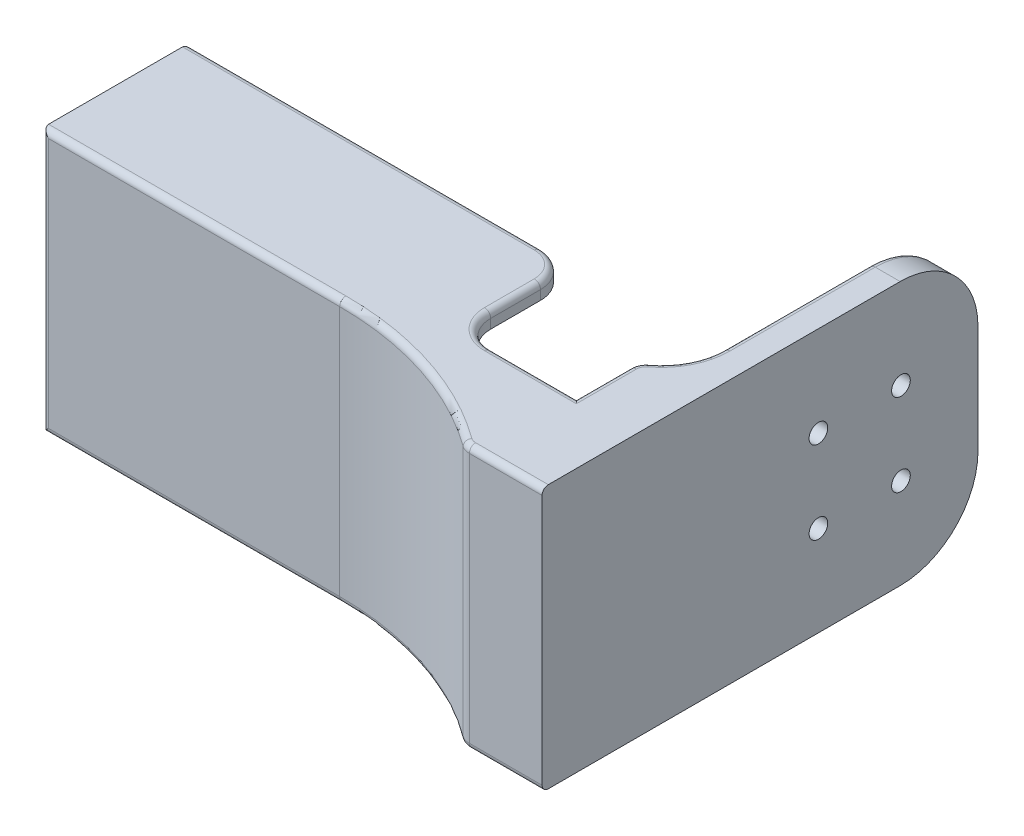
SolidWorks part; units mm, degrees
ref_plane "Alzado" through (0, 0, 0) normal (0, 0, 1) x (1, 0, 0)
ref_plane "Planta" through (0, 0, 0) normal (0, 1, 0) x (1, 0, 0)
ref_plane "Vista lateral" through (0, 0, 0) normal (1, 0, 0) x (0, 0, -1)
sketch "Croquis1" plane through (0, 0, 0) normal (0, 0, 1) x (1, 0, 0)
  line L1 (-59, -42.3) -> (59, -42.3)
  line L2 (-59, -42.3) -> (-59, 42.3)
  line L3 (-59, 42.3) -> (59, 42.3)
  line L4 (59, -42.3) -> (59, 42.3)
  line L5 (-59, -42.3) -> (59, 42.3) construction
  line L6 (-59, 42.3) -> (59, -42.3) construction
  point P0 (0, 0)
  dimension "D1" = 84.6
extrude "Saliente-Extruir1" add sketch "Croquis1" along normal blind 36
sketch "Croquis2" plane through (59, 0, 0) normal (1, 0, 0) x (0, 0, -1)
  line L1 (-36, 42.3) -> (0, 42.3) construction
  line L5 (0, -37.3) -> (0, 37.3)
  line L6 (0, -42.3) -> (0, 42.3) construction
  line L7 (0, 37.3) -> (-36, 37.3)
  line L8 (-36, -42.3) -> (-36, 42.3) construction
  line L9 (-36, 37.3) -> (-36, -37.3)
  line L10 (-36, -37.3) -> (0, -37.3)
  point P5 (0, 0)
  dimension "D1" = 5
extrude "Cortar-Extruir1" cut sketch "Croquis2" against normal blind 120
sketch "Croquis6" plane through (0, -42.3, 0) normal (0, -1, 0) x (1, 0, 0)
  line L0 (-59, 36) -> (59, 36) construction
  line L1 (-59, 0) -> (-59, 36)
  line L2 (-59, 36) -> (0, 36)
  arc A0 (-59, 0) -> (0, 36) centre (8.6236, -44.4803) cw
  point P9 (8.6236, -44.4803)
extrude "Cortar-Extruir3" cut sketch "Croquis6" against normal through all
sketch "Croquis7" plane through (0, 42.3, 0) normal (0, -1, 0) x (1, 0, 0)
  line L1 (59, 36) -> (59, 34)
  line L2 (59, 36) -> (59, 0) construction
  line L8 (-59, 0) -> (-59, 36)
  line L9 (-59, 36) -> (0, 36)
  arc A0 (-59, 0) -> (0, 36) centre (8.6236, -44.4803) cw
extrude "Saliente-Extruir2" add sketch "Croquis7" along normal through all separate body contours L9 A0 L8
sketch "Croquis8" plane through (0, 0, 36) normal (0, 0, 1) x (1, 0, 0)
  line L0 (-59, 42.3) -> (-59, -42.3)
  line L1 (-59, -42.3) -> (101.5, -42.3)
  line L2 (101.5, -42.3) -> (101.5, 42.3)
  line L3 (101.5, 42.3) -> (-59, 42.3)
  dimension "D1" = 160.5
extrude "Saliente-Extruir3" add sketch "Croquis8" along normal blind 5
sketch "Croquis9" plane through (-59, 0, 0) normal (-1, 0, 0) x (0, 0, 1)
  line L0 (0, 42.3) -> (41, 42.3)
  line L1 (41, 42.3) -> (41, -42.3)
  line L2 (41, -42.3) -> (0, -42.3)
  line L3 (0, -42.3) -> (0, 42.3)
extrude "Saliente-Extruir4" add sketch "Croquis9" along normal blind 5
sketch "Croquis10" plane through (0, 0, 36) normal (0, 0, -1) x (-1, 0, 0)
  line L0 (-101.5, 42.3) -> (-96.5, 42.3)
  line L1 (-101.5, 42.3) -> (-59, 42.3) construction
  line L2 (-96.5, 42.3) -> (-96.5, -42.3)
  line L3 (-59, -42.3) -> (-101.5, -42.3) construction
  line L4 (-96.5, -42.3) -> (-101.5, -42.3)
  line L5 (-101.5, -42.3) -> (-101.5, 42.3)
extrude "Saliente-Extruir5" add sketch "Croquis10" along normal blind 20
fillet "Redondeo2" radius 10 4 edges at (59, -39.8, 36) (59, -39.8, 0) (59, 39.8, 36) (59, 39.8, 0)
fillet "Redondeo4" radius 2 11 edges at (82.75, -42.3, 36) (61.9289, -42.3, 33.0711) (59, -42.3, 18) (56.0711, -42.3, 2.9289) (82.75, 42.3, 36) (61.9289, 42.3, 33.0711) (59, 42.3, 18) (56.0711, 42.3, 2.9289) (-7.5, -42.3, 0) (-64, 0, 0) (-7.5, 42.3, 0)
sketch "Croquis18" plane through (0, 0, 41) normal (0, 0, 1) x (1, 0, 0)
  line L0 (-64, 42.3) -> (-64, -42.3)
  line L1 (-64, -42.3) -> (101.5, -42.3)
  line L2 (101.5, -42.3) -> (101.5, 42.3)
  line L3 (101.5, -42.3) -> (101.5, 42.3) construction
  line L4 (101.5, 42.3) -> (-64, 42.3)
extrude "Saliente-Extruir9" add sketch "Croquis18" along normal blind 6
sketch "Croquis23" plane through (101.5, 0, 0) normal (1, 0, 0) x (0, 0, -1)
  line L0 (-47, 42.3) -> (-16, 42.3)
  line L1 (-16, 42.3) -> (-16, -42.3)
  line L2 (-16, -42.3) -> (-47, -42.3)
  line L3 (-47, -42.3) -> (-47, 42.3)
extrude "Saliente-Extruir12" add sketch "Croquis23" along normal blind 5
sketch "Croquis19" plane through (106.5, 0, 0) normal (1, 0, 0) x (0, 0, -1)
  line L0 (-47, 42.3) -> (73, 42.3)
  line L2 (-47, 42.3) -> (-47, -42.3)
  line L3 (-47, -42.3) -> (73, -42.3)
  line L4 (73, -42.3) -> (73, 42.3)
extrude "Saliente-Extruir10" add sketch "Croquis19" along normal blind 10
sketch "Croquis31" plane through (0, 42.3, 0) normal (0, 1, 0) x (1, 0, 0)
  line L0 (106.5, -16) -> (96.5, -16) construction
  line L1 (96.5, -16) -> (106.5, -16) construction
fillet "Redondeo6" radius 20 1 edges at (106.5, 0, 16)
fillet "Redondeo9" radius 5 1 edges at (96.5, 0, 16)
sketch "Croquis22" plane through (0, 0, 47) normal (0, 0, 1) x (1, 0, 0)
  line L0 (116.5, 42.3) -> (91.5, 42.3)
  line L1 (116.5, 42.3) -> (-64, 42.3) construction
  line L2 (91.5, 42.3) -> (91.5, -42.3)
  line L3 (-64, -42.3) -> (116.5, -42.3) construction
  line L4 (91.5, -42.3) -> (116.5, -42.3)
  line L5 (116.5, -42.3) -> (116.5, 42.3)
extrude "Saliente-Extruir11" add sketch "Croquis22" along normal blind 20
fillet "Redondeo7" radius 100 1 edges at (91.5, 0, 47)
fillet "Redondeo10" radius 5 1 edges at (91.5, 0, 67)
sketch "Croquis24" plane through (0, 42.3, 0) normal (0, 1, 0) x (1, 0, 0)
  line L0 (-64, -2) -> (-64, 10) construction
  line L1 (-64, -47) -> (-64, -2) construction
  line L2 (-64, 10) -> (99.396, 10) construction
  line L3 (-64, 10) -> (-64, 35) construction
  line L4 (-64, 35) -> (125.652, 35) construction
  arc A0 (-62, 0) -> (-64, -2) centre (-62, -2) ccw construction
sketch "Croquis25" plane through (106.5, 0, 0) normal (-1, 0, 0) x (0, 0, 1)
  line L0 (-35, 42.3) -> (-35, -42.3) construction
  line L1 (-10, 42.3) -> (-35, 42.3) construction
  line L2 (-1.3205, -42.3) -> (-73, -42.3) construction
sketch "Croquis26" plane through (116.5, 0, 0) normal (1, 0, 0) x (0, 0, -1)
  line L0 (21.75, 13.25) -> (48.25, 13.25) construction
  line L1 (21.75, -13.25) -> (21.75, 13.25) construction
  line L2 (48.25, 13.25) -> (48.25, -13.25) construction
  line L3 (21.75, -13.25) -> (48.25, -13.25) construction
  line L4 (35, 42.3) -> (35, -42.3) construction
  line L5 (35, 13.25) -> (35, -13.25) construction
  line L7 (-67, -42.3) -> (73, -42.3) construction
  line L8 (73, 42.3) -> (-67, 42.3) construction
  circle A0 centre (21.75, 13.25) radius 6
  circle A1 centre (48.25, 13.25) radius 6
  circle A2 centre (48.25, -13.25) radius 6
  circle A3 centre (21.75, -13.25) radius 6
  point P4 (59.5163, -0.2655)
  dimension "D1" = 12
  dimension "D2" = 12
  dimension "D3" = 12
  dimension "D4" = 12
  dimension "D6" = 29.05
  dimension "D7" = 29.05
  dimension "D5" = 26.5
  dimension "D8" = 26.5
extrude "Cortar-Extruir4" cut sketch "Croquis26" against normal through all
sketch "Croquis28" plane through (116.5, 0, 0) normal (1, 0, 0) x (0, 0, -1)
  circle A0 centre (21.75, 13.25) radius 6
  circle A1 centre (48.25, 13.25) radius 6
  circle A2 centre (21.75, -13.25) radius 6
  circle A3 centre (48.25, -13.25) radius 6
extrude "Saliente-Extruir14" add sketch "Croquis28" against normal blind 5
sketch "Croquis30" plane through (111.5, 0, 0) normal (-1, 0, 0) x (0, 0, 1)
  circle A0 centre (-48.25, 13.25) radius 3
  circle A1 centre (-21.75, 13.25) radius 3
  circle A2 centre (-48.25, -13.25) radius 3
  circle A3 centre (-21.75, -13.25) radius 3
extrude "Cortar-Extruir5" cut sketch "Croquis30" against normal through all
fillet "Redondeo11" radius 25 2 edges at (111.5, -42.3, -73) (111.5, 42.3, -73)
fillet "Redondeo12" radius 2 11 edges at (96.5, -42.3, 28.3397) (97.0279, -42.3, 16.4434) (104.3885, -42.3, 7.6238) (106.5, -42.3, -24.6603) (106.5, -34.9777, -65.6777) (106.5, 0, -73) (106.5, 34.9777, -65.6777) (106.5, 42.3, -24.6603) (97.0279, 42.3, 16.4434) (104.3885, 42.3, 7.6238) (96.5, 42.3, 28.3397)
fillet "Redondeo13" radius 2 9 edges at (104.8221, 42.3, 67) (91.6011, 42.3, 66.7559) (62.3607, 42.3, 51.881) (-16.25, -42.3, 47) (62.3607, -42.3, 51.881) (91.6011, -42.3, 66.7559) (-16.25, 42.3, 47) (-64, 0, 47) (104.8221, -42.3, 67)
